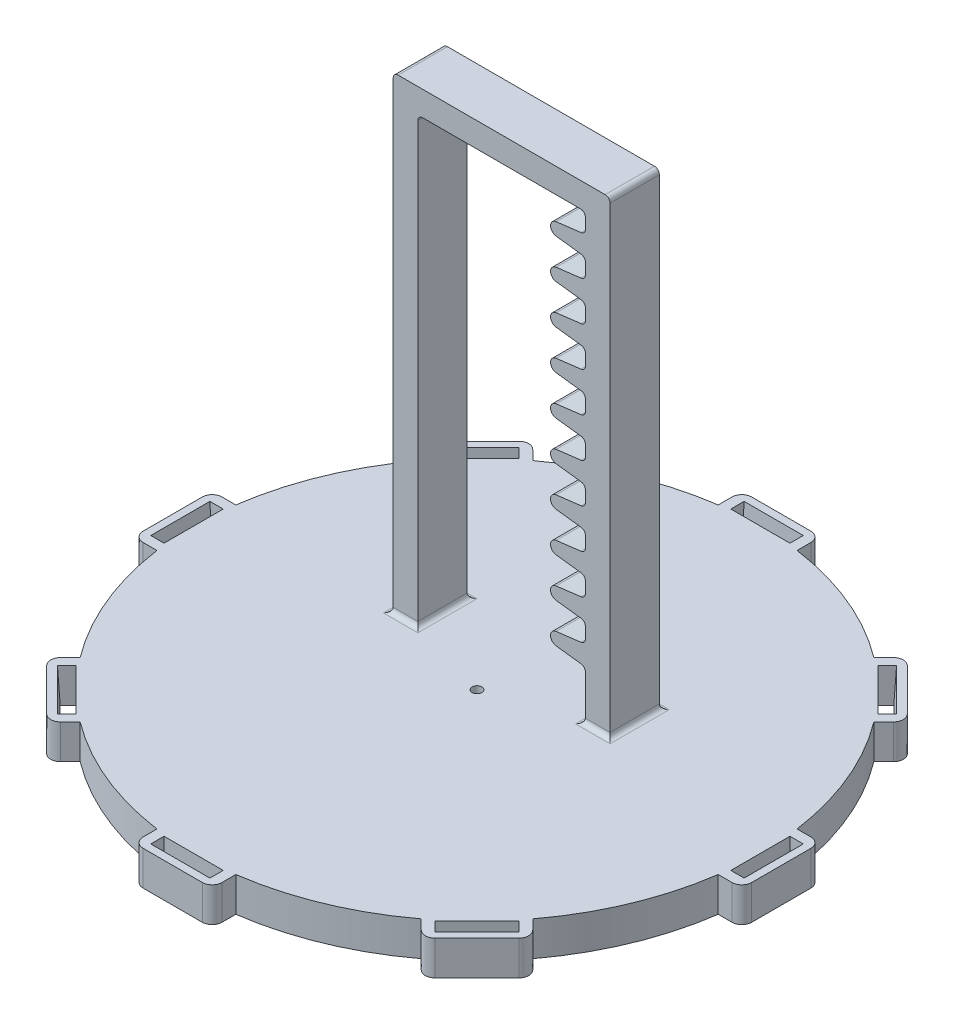
SolidWorks part; units mm, degrees
ref_plane "Front Plane" through (0, 0, 0) normal (0, 0, 1) x (1, 0, 0)
ref_plane "Top Plane" through (0, 0, 0) normal (0, 1, 0) x (1, 0, 0)
ref_plane "Right Plane" through (0, 0, 0) normal (1, 0, 0) x (0, 0, -1)
sketch "Sketch1" plane through (0, 0, 0) normal (0, 1, 0) x (1, 0, 0)
  line L0 (-8, 56.9408) -> (-8, 59.7408)
  line L1 (0, 57.5) -> (0, -57.5) construction
  line L2 (8, 56.9408) -> (8, 59.7408)
  line L3 (-6, 61.7408) -> (6, 61.7408)
  line L4 (39.4147, 47.8999) -> (47.8999, 39.4147)
  line L9 (34.6063, 45.9201) -> (36.5862, 47.8999)
  line L10 (45.9201, 34.6063) -> (47.8999, 36.5862)
  line L15 (61.7408, 6) -> (61.7408, -6)
  line L16 (56.9408, 8) -> (59.7408, 8)
  line L17 (56.9408, -8) -> (59.7408, -8)
  line L22 (47.8999, -39.4147) -> (39.4147, -47.8999)
  line L23 (45.9201, -34.6063) -> (47.8999, -36.5862)
  line L24 (34.6063, -45.9201) -> (36.5862, -47.8999)
  line L29 (6, -61.7408) -> (-6, -61.7408)
  line L30 (8, -56.9408) -> (8, -59.7408)
  line L31 (-8, -56.9408) -> (-8, -59.7408)
  line L36 (-39.4147, -47.8999) -> (-47.8999, -39.4147)
  line L37 (-34.6063, -45.9201) -> (-36.5862, -47.8999)
  line L38 (-45.9201, -34.6063) -> (-47.8999, -36.5862)
  line L43 (-61.7408, -6) -> (-61.7408, 6)
  line L44 (-56.9408, -8) -> (-59.7408, -8)
  line L45 (-56.9408, 8) -> (-59.7408, 8)
  line L50 (-47.8999, 39.4147) -> (-39.4147, 47.8999)
  line L51 (-45.9201, 34.6063) -> (-47.8999, 36.5862)
  line L52 (-34.6063, 45.9201) -> (-36.5862, 47.8999)
  arc A0 (-8, 56.9408) -> (-34.6063, 45.9201) centre (0, 0) ccw
  arc A1 (6, 61.7408) -> (8, 59.7408) centre (6, 59.7408) cw
  arc A2 (-6, 61.7408) -> (-8, 59.7408) centre (-6, 59.7408) ccw
  arc A3 (39.4147, 47.8999) -> (36.5862, 47.8999) centre (38.0005, 46.4857) ccw
  arc A4 (47.8999, 39.4147) -> (47.8999, 36.5862) centre (46.4857, 38.0005) cw
  arc A5 (61.7408, 6) -> (59.7408, 8) centre (59.7408, 6) ccw
  arc A6 (61.7408, -6) -> (59.7408, -8) centre (59.7408, -6) cw
  arc A7 (47.8999, -39.4147) -> (47.8999, -36.5862) centre (46.4857, -38.0005) ccw
  arc A8 (39.4147, -47.8999) -> (36.5862, -47.8999) centre (38.0005, -46.4857) cw
  arc A9 (6, -61.7408) -> (8, -59.7408) centre (6, -59.7408) ccw
  arc A10 (-6, -61.7408) -> (-8, -59.7408) centre (-6, -59.7408) cw
  arc A11 (-39.4147, -47.8999) -> (-36.5862, -47.8999) centre (-38.0005, -46.4857) ccw
  arc A12 (-47.8999, -39.4147) -> (-47.8999, -36.5862) centre (-46.4857, -38.0005) cw
  arc A13 (-61.7408, -6) -> (-59.7408, -8) centre (-59.7408, -6) ccw
  arc A14 (-61.7408, 6) -> (-59.7408, 8) centre (-59.7408, 6) cw
  arc A15 (-47.8999, 39.4147) -> (-47.8999, 36.5862) centre (-46.4857, 38.0005) ccw
  arc A16 (-39.4147, 47.8999) -> (-36.5862, 47.8999) centre (-38.0005, 46.4857) cw
  arc A17 (-45.9201, 34.6063) -> (-56.9408, 8) centre (0, 0) ccw
  arc A18 (-56.9408, -8) -> (-45.9201, -34.6063) centre (0, 0) ccw
  arc A19 (34.6063, 45.9201) -> (8, 56.9408) centre (0, 0) ccw
  arc A20 (-34.6063, -45.9201) -> (-8, -56.9408) centre (0, 0) ccw
  arc A21 (8, -56.9408) -> (34.6063, -45.9201) centre (0, 0) ccw
  arc A22 (45.9201, -34.6063) -> (56.9408, -8) centre (0, 0) ccw
  arc A23 (56.9408, 8) -> (45.9201, 34.6063) centre (0, 0) ccw
  point P11 (8, 61.7408)
  point P14 (-8, 61.7408)
  point P17 (-8, 58.3408)
  point P98 (0, 0)
  dimension "D1" = 115
  dimension "D2" = 2
  dimension "D3" = 16
  dimension "D4" = 2.8
  dimension "D7" = 8
extrude "Boss-Extrude1" add sketch "Sketch1" along normal blind 7
sketch "Sketch2" plane through (0, 7, 0) normal (0, 1, 0) x (1, 0, 0)
  line L0 (-57.5, 0) -> (57.5, 0) construction
  line L1 (0, 0) -> (0, 10) construction
  line L7 (17, 5) -> (22, 5)
  line L14 (0, 10) -> (29.7122, 10) construction
  line L15 (0, 10) -> (-19.5, 10) construction
  line L17 (17, 5) -> (17, 15)
  line L18 (-22, 15) -> (-17, 15)
  line L19 (-22, 15) -> (-22, 5)
  line L20 (-22, 5) -> (-17, 5)
  line L21 (-17, 15) -> (-17, 5)
  line L22 (-22, 15) -> (-17, 5) construction
  line L23 (-22, 5) -> (-17, 15) construction
  line L24 (17, 15) -> (22, 15)
  line L25 (22, 5) -> (22, 15)
  line L26 (17, 5) -> (22, 15) construction
  line L27 (17, 15) -> (22, 5) construction
  circle A0 centre (0, 0) radius 57.5 construction
  point P8 (19.5, 10)
  dimension "D1" = 10
  dimension "D2" = 17
  dimension "D3" = 17
  dimension "D4" = 10
  dimension "D5" = 5
  dimension "D6" = 10
  dimension "D7" = 5
extrude "Boss-Extrude2" add sketch "Sketch2" along normal blind 95
sketch "Sketch15" plane through (0, 0, 0) normal (0, -1, 0) x (1, 0, 0)
  circle A0 centre (0, 0) radius 1
  dimension "D1" = 2
extrude "Cut-Extrude3" cut sketch "Sketch15" along direction (0, 1, 0) on the side against the normal up to surface (7 mm away) contours A0 up to face at (0, 7, 0)
sketch "Sketch16" plane through (0, 0, 0) normal (0, -1, 0) x (1, 0, 0)
  line L1 (-6, 59.8) -> (6, 59.8)
  line L2 (-6, 59.8) -> (-6, 57.5)
  line L3 (-6, 57.5) -> (6, 57.5)
  line L4 (6, 59.8) -> (6, 57.5)
  point P5 (0, 57.5)
  dimension "D1" = 2.3
  dimension "D2" = 12
  dimension "D3" = 57.5
sketch "Sketch17" plane through (0, 7, 0) normal (0, 1, 0) x (1, 0, 0)
  line L0 (-6, -57.5) -> (6, -57.5) construction
  line L1 (-6, -57.5) -> (6, -57.5)
  line L2 (-6, -57.5) -> (-6, -60.2)
  line L3 (-6, -60.2) -> (6, -60.2)
  line L4 (6, -60.2) -> (6, -57.5)
  dimension "D1" = 2.7
ref_axis "Axis1" through (0, 107.1, 0) along (0, -1, 0)
loft "Cut-Loft2" cut profiles "Sketch16", "Sketch17" connector at (6, 0, 59.8) connector at (6, 7, 60.2)
pattern_circular "CirPattern1" count 8 over 360 about axis through (0, 107.1, 0) along (0, -1, 0) of "Cut-Loft2"
sketch "Sketch18" plane through (-17, 0, 0) normal (1, 0, 0) x (0, 0, -1)
  line L0 (15, 102) -> (15, 7) construction
  line L1 (5, 102) -> (15, 102)
  line L2 (5, 102) -> (5, 97)
  line L3 (5, 97) -> (15, 97)
  line L4 (15, 102) -> (15, 97)
  dimension "D1" = 5
extrude "Boss-Extrude3" add sketch "Sketch18" along normal up to surface (34 mm away) up to face at (17, 54.5, -10)
sketch "Sketch19" plane through (0, 0, -15) normal (0, 0, -1) x (-1, 0, 0)
  line L0 (-17, 93) -> (-11.0447, 92.2688)
  line L1 (-17, 97) -> (-17, 7) construction
  line L4 (-11, 91) -> (-19.8185, 91) construction
  line L5 (-17, 89) -> (-11.0447, 89.7312)
  line L6 (-17, 93) -> (-17, 89)
  arc A1 (-11.0447, 92.2688) -> (-11.0447, 89.7312) centre (-11.2005, 91) cw
  dimension "D1" = 6
  dimension "D4" = 4
  dimension "D2" = 7
  dimension "D3" = 4
extrude "Boss-Extrude4" add sketch "Sketch19" against normal blind 10
fillet "Fillet1" radius 1 2 edges at (17, 93, -10) (17, 89, -10)
fillet "Fillet2" radius 1 12 edges at (-22, 102, -10) (22, 102, -10) (17, 7, -10) (19.5, 7, -15) (19.5, 7, -5) (22, 7, -10) (-19.5, 7, -5) (-19.5, 7, -15) (-22, 7, -10) (-17, 7, -10) (-17, 97, -10) (17, 97, -10)
pattern_linear "LPattern2" count 10 spacing 8 along (0, -1, 0) of "Fillet1", "Boss-Extrude4"
equation "\"85.00.00mm\"=8500"
